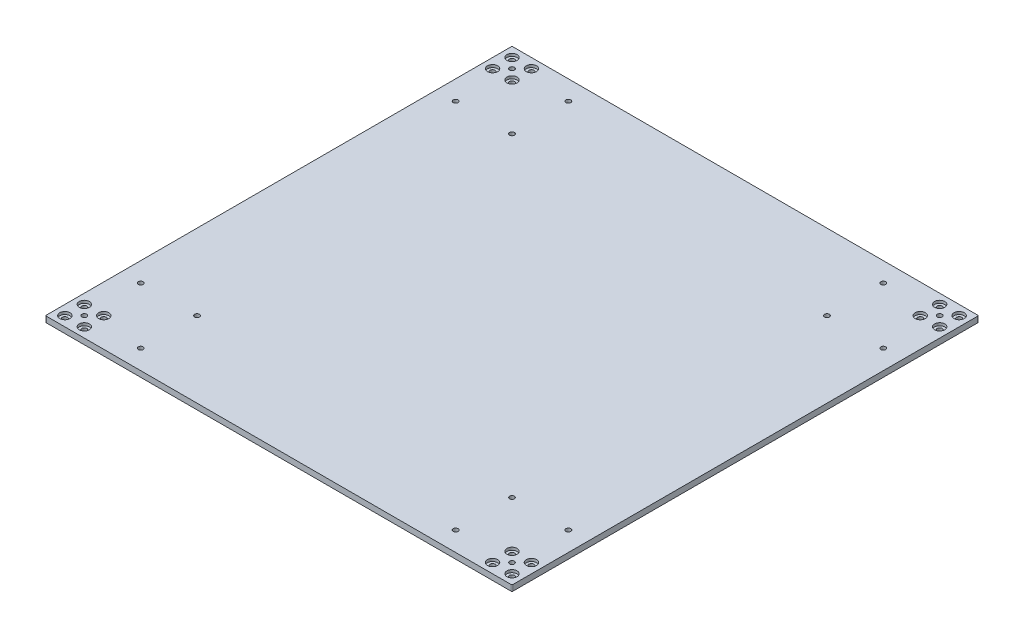
SolidWorks part; units mm, degrees
material "ASTM A36 Steel"
ref_plane "Front Plane" through (0, 0, 0) normal (0, 0, 1) x (1, 0, 0)
ref_plane "Top Plane" through (0, 0, 0) normal (0, 1, 0) x (1, 0, 0)
ref_plane "Right Plane" through (0, 0, 0) normal (1, 0, 0) x (0, 0, -1)
sketch "Sketch1" plane through (0, 0, 0) normal (0, 1, 0) x (1, 0, 0)
  line L1 (240, -240) -> (-240, -240)
  line L2 (240, -240) -> (240, 240)
  line L3 (240, 240) -> (-240, 240)
  line L4 (-240, -240) -> (-240, 240)
  line L5 (240, -240) -> (-240, 240) construction
  line L6 (240, 240) -> (-240, -240) construction
  point P0 (0, 0)
  dimension "D1" = 480
extrude "Boss-Extrude1" add sketch "Sketch1" along normal blind 6
sketch "Sketch2" plane through (0, 6, 0) normal (0, 1, 0) x (1, 0, 0)
  line L1 (-200, 200) -> (-240, 200)
  line L2 (-200, 200) -> (-200, 240)
  line L3 (-200, 240) -> (-240, 240)
  line L4 (-240, 200) -> (-240, 240)
  line L5 (-200, 200) -> (-240, 240) construction
  line L6 (-200, 240) -> (-240, 200) construction
  line L7 (-210, 210) -> (-230, 210)
  line L8 (-210, 210) -> (-210, 230)
  line L9 (-210, 230) -> (-230, 230)
  line L10 (-230, 210) -> (-230, 230)
  line L11 (-210, 210) -> (-230, 230) construction
  line L12 (-210, 230) -> (-230, 210) construction
  point P0 (-220, 220)
  point P6 (-220, 220)
  dimension "D1" = 40
  dimension "D2" = 20
hole_wizard "CBORE for M5 SBHCS1" positions "Sketch5" profile "Sketch6" counterbore size "M5" standard "ANSI Metric" end condition through all
sketch "Sketch5" plane through (0, 6, 0) normal (0, 1, 0) x (1, 0, 0)
  point P0 (-230, 230)
  point P3 (-210, 230)
  point P6 (-210, 210)
  point P9 (-230, 210)
sketch "Sketch6" plane through (-230, 6, -230) normal (1, 0, 0) x (0, 0, 1)
  line L0 (0, 0) -> (0, 6)
  line L1 (0, 6) -> (2.65, 6)
  line L3 (2.65, 6) -> (2.65, 2.75)
  line L4 (2.65, 2.75) -> (5.25, 2.75)
  line L5 (5.25, 2.75) -> (5.25, 0)
  line L7 (5.25, 0) -> (0, 0)
  line L11 (0, -6.35) -> (0, 107.95) construction
  dimension "Thru Hole Dia." = 5.3
  dimension "Thru Hole Depth" = 6
  dimension "C'Bore Dia." = 10.5
  dimension "C'Bore Depth" = 2.75
sketch "Sketch9" plane through (0, 6, 0) normal (0, 1, 0) x (1, 0, 0)
  line L0 (-230, 210) -> (-210, 230) construction
  line L1 (-154.5, 154.5) -> (-227.5, 154.5)
  line L2 (-154.5, 154.5) -> (-154.5, 227.5)
  line L3 (-154.5, 227.5) -> (-227.5, 227.5)
  line L4 (-227.5, 154.5) -> (-227.5, 227.5)
  line L5 (-154.5, 154.5) -> (-227.5, 227.5) construction
  line L6 (-154.5, 227.5) -> (-227.5, 154.5) construction
  line L7 (-162, 162) -> (-220, 162)
  line L8 (-162, 162) -> (-162, 220)
  line L9 (-162, 220) -> (-220, 220)
  line L10 (-220, 162) -> (-220, 220)
  line L11 (-162, 162) -> (-220, 220) construction
  line L12 (-162, 220) -> (-220, 162) construction
  point P0 (-191, 191)
  point P5 (-191, 191)
  dimension "D1" = 73
  dimension "D2" = 58
hole_wizard "Tap Drill for M6x1.0 Tap1" positions "Sketch10" profile "Sketch11" hole size "M6x1.0" standard "ANSI Metric" end condition through all
sketch "Sketch10" plane through (0, 6, 0) normal (0, 1, 0) x (1, 0, 0)
  point P0 (-220, 220)
  point P3 (-162, 220)
  point P6 (-162, 162)
  point P9 (-220, 162)
sketch "Sketch11" plane through (-220, 6, -220) normal (1, 0, 0) x (0, 0, 1)
  line L0 (0, 0) -> (0, 6)
  line L1 (0, 6) -> (2.5, 6)
  line L2 (2.5, 6) -> (2.5, 0)
  line L5 (2.5, 0) -> (0, 0)
  line L11 (0, -6.35) -> (0, 107.95) construction
  dimension "Thru Hole Dia." = 5
  dimension "Thru Hole Depth" = 6
ref_axis "Axis1" through (0, 8.4, 0) along (0, -1, 0)
pattern_circular "CirPattern1" count 4 over 360 about axis through (0, 8.4, 0) along (0, -1, 0) of "CBORE for M5 SBHCS1", "Tap Drill for M6x1.0 Tap1"
fillet "Fillet1" radius 1 4 edges at (-240, 3, -240) (240, 3, -240) (240, 3, 240) (-240, 3, 240)
